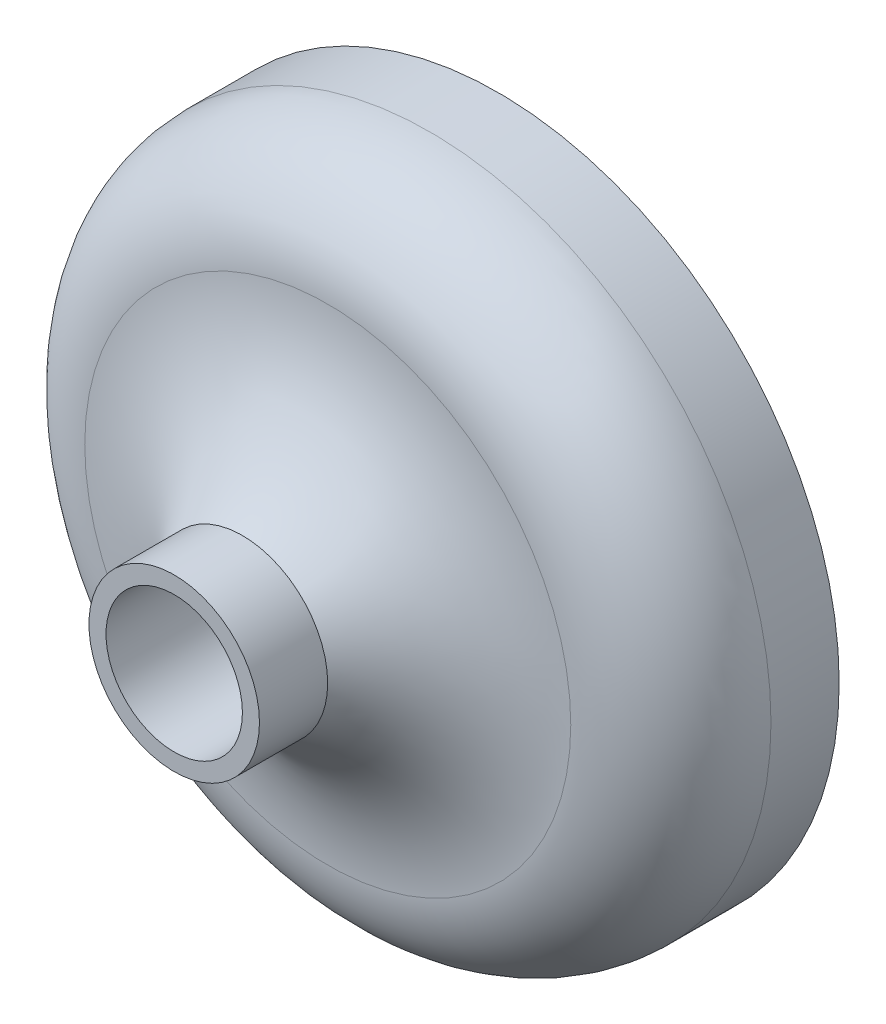
SolidWorks part; units mm, degrees
ref_plane "Front Plane" through (0, 0, 0) normal (0, 0, 1) x (1, 0, 0)
ref_plane "Top Plane" through (0, 0, 0) normal (0, 1, 0) x (1, 0, 0)
ref_plane "Right Plane" through (0, 0, 0) normal (1, 0, 0) x (0, 0, -1)
sketch "Sketch1" plane through (0, 0, 0) normal (0, 0, 1) x (1, 0, 0)
  circle A0 centre (0, 0) radius 100
  circle A1 centre (0, 0) radius 95
  dimension "D1" = 200
  dimension "D2" = 190
extrude "Boss-Extrude1" add sketch "Sketch1" along normal blind 25
sketch "Sketch2" plane through (0, 0, 25) normal (0, 0, 1) x (1, 0, 0)
  circle A0 centre (0, 0) radius 100
extrude "Boss-Extrude2" add sketch "Sketch2" along normal blind 25
sketch "Sketch3" plane through (0, 0, 50) normal (0, 0, 1) x (1, 0, 0)
  circle A0 centre (0, 0) radius 20
  dimension "D1" = 40
extrude "Cut-Extrude1" cut sketch "Sketch3" against normal blind 25
sketch "Sketch4" plane through (0, 0, 50) normal (0, 0, 1) x (1, 0, 0)
  circle A0 centre (0, 0) radius 20
  circle A1 centre (0, 0) radius 25
  dimension "D1" = 50
extrude "Boss-Extrude3" add sketch "Sketch4" along normal blind 25
fillet "Fillet1" radius 30 1 edges at (100, 0, 50)
fillet "Fillet2" radius 120 1 edges at (95, 0, 25)
fillet "Fillet3" radius 60 1 edges at (25, 0, 50)
sketch "Sketch5" plane through (0, 0, 75) normal (0, 0, 1) x (1, 0, 0)
  circle A0 centre (0, 0) radius 25
  circle A1 centre (0, 0) radius 20
extrude "Boss-Extrude4" add sketch "Sketch5" along normal blind 20
